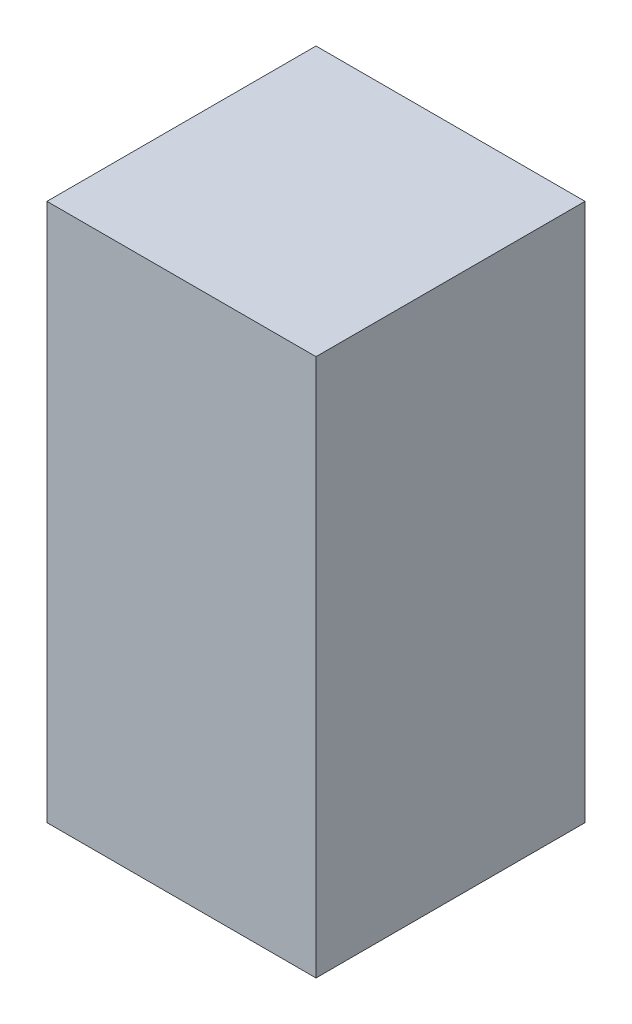
SolidWorks part; units mm, degrees
ref_plane "Front Plane" through (0, 0, 0) normal (0, 0, 1) x (1, 0, 0)
ref_plane "Top Plane" through (0, 0, 0) normal (0, 1, 0) x (1, 0, 0)
ref_plane "Right Plane" through (0, 0, 0) normal (1, 0, 0) x (0, 0, -1)
sketch "Sketch1" plane through (0, 0, 0) normal (0, 1, 0) x (1, 0, 0)
  line L1 (0, 0) -> (10, 0)
  line L2 (0, 0) -> (0, 10)
  line L3 (0, 10) -> (10, 10)
  line L4 (10, 0) -> (10, 10)
  dimension "D1" = 10
  dimension "D2" = 10
extrude "Boss-Extrude1" add sketch "Sketch1" along normal blind 20
